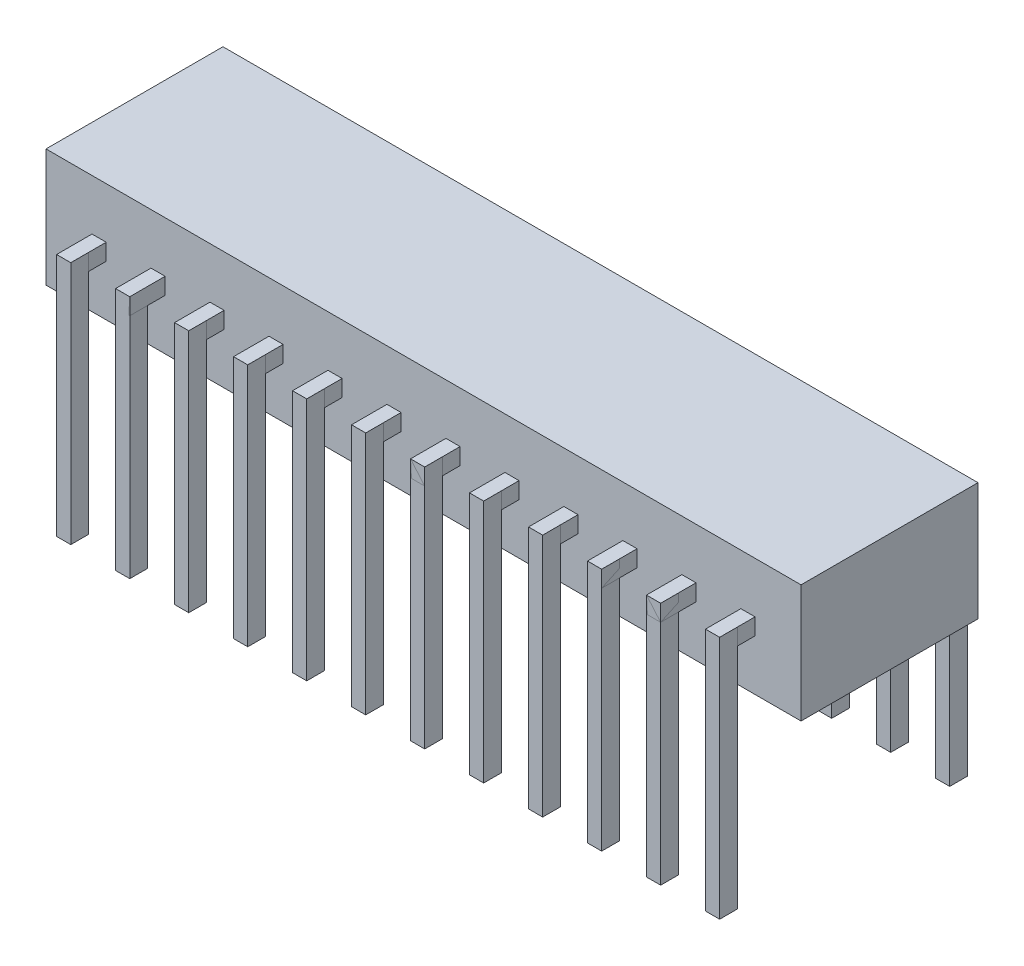
SolidWorks part; units mm, degrees
ref_plane "Front Plane" through (0, 0, 0) normal (0, 0, 1) x (1, 0, 0)
ref_plane "Top Plane" through (0, 0, 0) normal (0, 1, 0) x (1, 0, 0)
ref_plane "Right Plane" through (0, 0, 0) normal (1, 0, 0) x (0, 0, -1)
sketch "Sketch2" plane through (0, 0, 0) normal (0, 1, 0) x (1, 0, 0)
  line L6 (-20309.113, 11132.2225) -> (11690.887, 11132.2225)
  line L9 (11690.887, 11132.2225) -> (11690.887, 3632.2225)
  line L11 (-20309.113, 3632.2225) -> (-20309.113, 11132.2225)
  line L12 (-5259.113, 2132.2225) -> (-5259.113, 3632.2225)
  line L13 (-859.113, 2132.2225) -> (-259.113, 2132.2225)
  line L14 (-259.113, 2132.2225) -> (-259.113, 3632.2225)
  line L15 (-859.113, 3632.2225) -> (-259.113, 3632.2225)
  line L16 (-859.113, 2132.2225) -> (-859.113, 3632.2225)
  line L17 (-3359.113, 2132.2225) -> (-2759.113, 2132.2225)
  line L18 (-2759.113, 2132.2225) -> (-2759.113, 3632.2225)
  line L19 (-3359.113, 3632.2225) -> (-2759.113, 3632.2225)
  line L20 (-3359.113, 2132.2225) -> (-3359.113, 3632.2225)
  line L21 (-5259.113, 3632.2225) -> (-5859.113, 3632.2225)
  line L22 (-20309.113, 3632.2225) -> (11690.887, 3632.2225)
  line L23 (-5859.113, 2132.2225) -> (-5859.113, 3632.2225)
  line L24 (-5259.113, 2132.2225) -> (-5859.113, 2132.2225)
  line L25 (-7759.113, 2132.2225) -> (-7759.113, 3632.2225)
  line L26 (-7759.113, 3632.2225) -> (-8359.113, 3632.2225)
  line L27 (-8359.113, 2132.2225) -> (-8359.113, 3632.2225)
  line L28 (-7759.113, 2132.2225) -> (-8359.113, 2132.2225)
  line L29 (-10859.113, 2132.2225) -> (-10259.113, 2132.2225)
  line L30 (-10259.113, 2132.2225) -> (-10259.113, 3632.2225)
  line L31 (-10859.113, 3632.2225) -> (-10259.113, 3632.2225)
  line L32 (-10859.113, 2132.2225) -> (-10859.113, 3632.2225)
  line L33 (-13359.113, 2132.2225) -> (-12759.113, 2132.2225)
  line L34 (-12759.113, 2132.2225) -> (-12759.113, 3632.2225)
  line L35 (-13359.113, 3632.2225) -> (-12759.113, 3632.2225)
  line L36 (-15259.113, 2132.2225) -> (-15259.113, 3632.2225)
  line L37 (-15259.113, 3632.2225) -> (-15859.113, 3632.2225)
  line L38 (-15859.113, 2132.2225) -> (-15859.113, 3632.2225)
  line L39 (-15259.113, 2132.2225) -> (-15859.113, 2132.2225)
  line L40 (-17759.113, 2132.2225) -> (-17759.113, 3632.2225)
  line L41 (-17759.113, 3632.2225) -> (-18359.113, 3632.2225)
  line L42 (-18359.113, 2132.2225) -> (-18359.113, 3632.2225)
  line L43 (-17759.113, 2132.2225) -> (-18359.113, 2132.2225)
  line L44 (-13359.113, 2132.2225) -> (-13359.113, 3632.2225)
  line L45 (-13359.113, 12632.2225) -> (-13359.113, 11132.2225)
  line L46 (-17759.113, 12632.2225) -> (-18359.113, 12632.2225)
  line L47 (-18359.113, 12632.2225) -> (-18359.113, 11132.2225)
  line L48 (-17759.113, 11132.2225) -> (-18359.113, 11132.2225)
  line L49 (-17759.113, 12632.2225) -> (-17759.113, 11132.2225)
  line L50 (-15259.113, 12632.2225) -> (-15859.113, 12632.2225)
  line L51 (-15859.113, 12632.2225) -> (-15859.113, 11132.2225)
  line L52 (-15259.113, 11132.2225) -> (-15859.113, 11132.2225)
  line L53 (-15259.113, 12632.2225) -> (-15259.113, 11132.2225)
  line L54 (-13359.113, 11132.2225) -> (-12759.113, 11132.2225)
  line L55 (-12759.113, 12632.2225) -> (-12759.113, 11132.2225)
  line L56 (-13359.113, 12632.2225) -> (-12759.113, 12632.2225)
  line L57 (-10859.113, 12632.2225) -> (-10859.113, 11132.2225)
  line L58 (-10859.113, 11132.2225) -> (-10259.113, 11132.2225)
  line L59 (-10259.113, 12632.2225) -> (-10259.113, 11132.2225)
  line L60 (-10859.113, 12632.2225) -> (-10259.113, 12632.2225)
  line L61 (-7759.113, 12632.2225) -> (-8359.113, 12632.2225)
  line L62 (-8359.113, 12632.2225) -> (-8359.113, 11132.2225)
  line L63 (-7759.113, 11132.2225) -> (-8359.113, 11132.2225)
  line L64 (-7759.113, 12632.2225) -> (-7759.113, 11132.2225)
  line L65 (-5259.113, 12632.2225) -> (-5859.113, 12632.2225)
  line L66 (-5859.113, 12632.2225) -> (-5859.113, 11132.2225)
  line L67 (-5259.113, 11132.2225) -> (-5859.113, 11132.2225)
  line L68 (-3359.113, 12632.2225) -> (-3359.113, 11132.2225)
  line L69 (-3359.113, 11132.2225) -> (-2759.113, 11132.2225)
  line L70 (-2759.113, 12632.2225) -> (-2759.113, 11132.2225)
  line L71 (-3359.113, 12632.2225) -> (-2759.113, 12632.2225)
  line L72 (-859.113, 12632.2225) -> (-859.113, 11132.2225)
  line L73 (-859.113, 11132.2225) -> (-259.113, 11132.2225)
  line L74 (-259.113, 12632.2225) -> (-259.113, 11132.2225)
  line L75 (-859.113, 12632.2225) -> (-259.113, 12632.2225)
  line L76 (-5259.113, 12632.2225) -> (-5259.113, 11132.2225)
  line L77 (-18359.113, 2882.2225) -> (-17759.113, 2882.2225)
  line L78 (-15859.113, 2882.2225) -> (-15259.113, 2882.2225)
  line L79 (-13359.113, 2882.2225) -> (-12759.113, 2882.2225)
  line L80 (-10859.113, 2882.2225) -> (-10259.113, 2882.2225)
  line L81 (-8359.113, 2882.2225) -> (-7759.113, 2882.2225)
  line L82 (-5859.113, 2882.2225) -> (-5259.113, 2882.2225)
  line L83 (-3359.113, 2882.2225) -> (-2759.113, 2882.2225)
  line L84 (-859.113, 2882.2225) -> (-259.113, 2882.2225)
  line L85 (-259.113, 11882.2225) -> (-859.113, 11882.2225)
  line L86 (9140.887, 11882.2225) -> (9740.887, 11882.2225)
  line L87 (-2759.113, 11882.2225) -> (-3359.113, 11882.2225)
  line L88 (-5259.113, 11882.2225) -> (-5859.113, 11882.2225)
  line L89 (-7759.113, 11882.2225) -> (-8359.113, 11882.2225)
  line L90 (-10259.113, 11882.2225) -> (-10859.113, 11882.2225)
  line L92 (-12759.113, 11882.2225) -> (-13359.113, 11882.2225)
  line L93 (-15259.113, 11882.2225) -> (-15859.113, 11882.2225)
  line L94 (-17759.113, 11882.2225) -> (-18359.113, 11882.2225)
  line L95 (6640.887, 11882.2225) -> (7240.887, 11882.2225)
  line L96 (4140.887, 11882.2225) -> (4740.887, 11882.2225)
  line L97 (1640.887, 11882.2225) -> (2240.887, 11882.2225)
  line L98 (2240.887, 2882.2225) -> (1640.887, 2882.2225)
  line L99 (4740.887, 2882.2225) -> (4140.887, 2882.2225)
  line L100 (7240.887, 2882.2225) -> (6640.887, 2882.2225)
  line L101 (9740.887, 2882.2225) -> (9140.887, 2882.2225)
  line L102 (6640.887, 12632.2225) -> (6640.887, 11132.2225)
  line L103 (2240.887, 12632.2225) -> (1640.887, 12632.2225)
  line L104 (1640.887, 12632.2225) -> (1640.887, 11132.2225)
  line L105 (2240.887, 11132.2225) -> (1640.887, 11132.2225)
  line L106 (2240.887, 12632.2225) -> (2240.887, 11132.2225)
  line L107 (4740.887, 12632.2225) -> (4140.887, 12632.2225)
  line L108 (4140.887, 12632.2225) -> (4140.887, 11132.2225)
  line L109 (4740.887, 11132.2225) -> (4140.887, 11132.2225)
  line L110 (4740.887, 12632.2225) -> (4740.887, 11132.2225)
  line L111 (6640.887, 11132.2225) -> (7240.887, 11132.2225)
  line L112 (7240.887, 12632.2225) -> (7240.887, 11132.2225)
  line L113 (6640.887, 12632.2225) -> (7240.887, 12632.2225)
  line L114 (9140.887, 12632.2225) -> (9140.887, 11132.2225)
  line L115 (9140.887, 11132.2225) -> (9740.887, 11132.2225)
  line L116 (9740.887, 12632.2225) -> (9740.887, 11132.2225)
  line L117 (9140.887, 12632.2225) -> (9740.887, 12632.2225)
  line L118 (9140.887, 2132.2225) -> (9740.887, 2132.2225)
  line L119 (9740.887, 2132.2225) -> (9740.887, 3632.2225)
  line L120 (9140.887, 3632.2225) -> (9740.887, 3632.2225)
  line L121 (9140.887, 2132.2225) -> (9140.887, 3632.2225)
  line L122 (6640.887, 2132.2225) -> (7240.887, 2132.2225)
  line L123 (7240.887, 2132.2225) -> (7240.887, 3632.2225)
  line L124 (6640.887, 3632.2225) -> (7240.887, 3632.2225)
  line L125 (4740.887, 2132.2225) -> (4740.887, 3632.2225)
  line L126 (4740.887, 3632.2225) -> (4140.887, 3632.2225)
  line L127 (4140.887, 2132.2225) -> (4140.887, 3632.2225)
  line L128 (4740.887, 2132.2225) -> (4140.887, 2132.2225)
  line L129 (2240.887, 2132.2225) -> (2240.887, 3632.2225)
  line L130 (2240.887, 3632.2225) -> (1640.887, 3632.2225)
  line L131 (1640.887, 2132.2225) -> (1640.887, 3632.2225)
  line L132 (2240.887, 2132.2225) -> (1640.887, 2132.2225)
  line L133 (6640.887, 2132.2225) -> (6640.887, 3632.2225)
extrude "Boss-Extrude1" add sketch "Sketch2" along normal mid plane 700 contours L49 L48 L47 L46 | L53 L52 L51 L50 | L55 L54 L45 L56 | L59 L58 L57 L60 | L64 L63 L62 L61 | L76 L67 L66 L65 | L70 L69 L68 L71 | L74 L73 L72 L75 | L106 L105 L104 L103 | L110 L109 L108 L107 | L112 L111 L102 L113 | L116 L115 L114 L117 | L119 L120 L121 L118 | L123 L124 L133 L122 | L125 L126 L127 L128 | L129 L130 L131 L132 | L14 L15 L16 L13 | L18 L19 L20 L17 | L12 L21 L23 L24 | L25 L26 L27 L28 | L30 L31 L32 L29 | L34 L35 L44 L33 | L36 L37 L38 L39 | L40 L41 L42 L43
extrude "Boss-Extrude2" add sketch "Sketch2<16>" against normal blind 10000 and the other way blind 345 separate body contours L77 L42 L43 L40 | L78 L38 L39 L36 | L79 L44 L33 L34 | L80 L32 L29 L30 | L81 L27 L28 L25 | L82 L23 L24 L12 | L83 L20 L17 L18 | L84 L16 L13 L14 | L132 L129 L98 L131 | L128 L125 L99 L127 | L133 L122 L123 L100 | L121 L118 L119 L101 | L117 L114 L86 L116 | L113 L102 L95 L112 | L110 L107 L108 L96 | L106 L103 L104 L97 | L94 L49 L46 L47 | L93 L53 L50 L51 | L92 L55 L56 L45 | L90 L59 L60 L57 | L89 L64 L61 L62 | L88 L76 L65 L66 | L87 L70 L71 L68 | L85 L74 L75 L72 region at (-18059.113, 0, -12257.2225) region at (-18059.113, 0, -2507.2225) region at (-15559.113, 0, -12257.2225) region at (-15559.113, 0, -2507.2225) region at (-13059.113, 0, -12257.2225) region at (-13059.113, 0, -2507.2225) region at (-10559.113, 0, -12257.2225) region at (-10559.113, 0, -2507.2225) region at (-8059.113, 0, -12257.2225) region at (-8059.113, 0, -2507.2225) region at (-5559.113, 0, -12257.2225) region at (-5559.113, 0, -2507.2225) region at (-3059.113, 0, -12257.2225) region at (-3059.113, 0, -2507.2225) region at (-559.113, 0, -12257.2225) region at (-559.113, 0, -2507.2225) region at (1940.887, 0, -12257.2225) region at (1940.887, 0, -2507.2225) region at (4440.887, 0, -12257.2225) region at (4440.887, 0, -2507.2225) region at (6940.887, 0, -12257.2225) region at (6940.887, 0, -2507.2225) region at (9440.887, 0, -12257.2225) region at (9440.887, 0, -2507.2225)
sketch "Sketch2<16>" plane through (0, 0, 0) normal (0, 1, 0) x (1, 0, 0) same geometry as "Sketch2"
extrude "Boss-Extrude3" add sketch "Sketch2<17>" along normal mid plane 5000 separate body contours L11 L22 L21 L19 L15 L9 L6 region at (-4309.113, 0, -7382.2225)
sketch "Sketch2<17>" plane through (0, 0, 0) normal (0, 1, 0) x (1, 0, 0) same geometry as "Sketch2"
